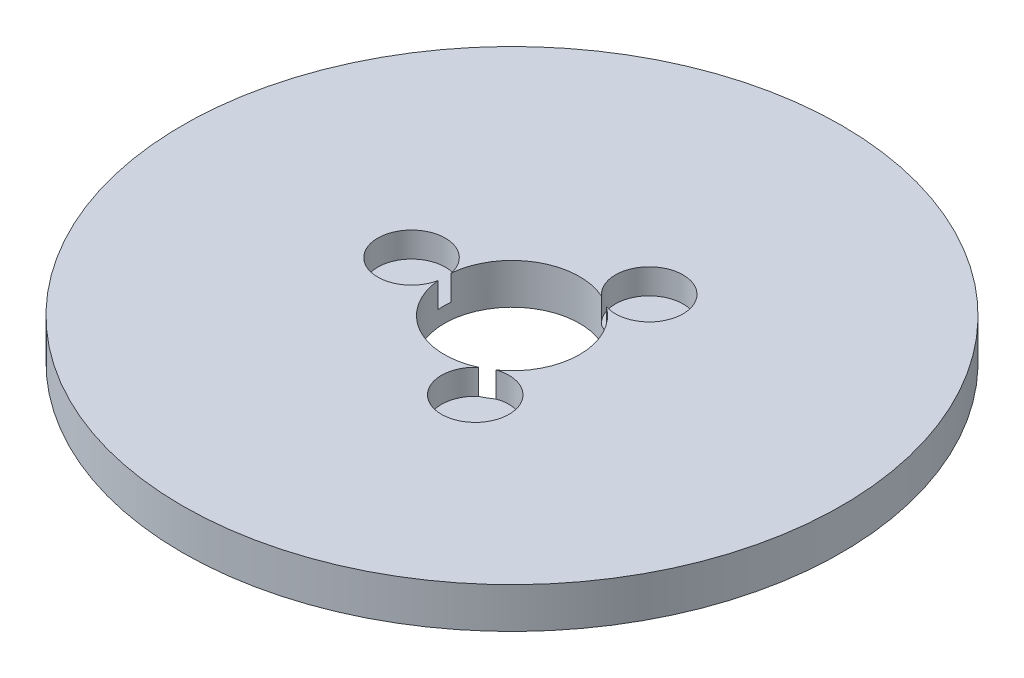
SolidWorks part; units mm, degrees
ref_plane "Front Plane" through (0, 0, 0) normal (0, 0, 1) x (1, 0, 0)
ref_plane "Top Plane" through (0, 0, 0) normal (0, 1, 0) x (1, 0, 0)
ref_plane "Right Plane" through (0, 0, 0) normal (1, 0, 0) x (0, 0, -1)
sketch "Sketch1" plane through (0, 0, 0) normal (0, 1, 0) x (1, 0, 0)
  circle A0 centre (0, 0) radius 97.5
  dimension "FLANGE_OD" = 195
extrude "Boss-Extrude1" add sketch "Sketch1" along normal blind 12
sketch "Sketch2" plane through (0, 0, 0) normal (0, 1, 0) x (1, 0, 0)
  circle A0 centre (0, 0) radius 20
  dimension "BORE_D" = 40
extrude "Cut-Extrude1" cut sketch "Sketch2" along normal through all
sketch "Sketch3" plane through (0, 12, 0) normal (0, 1, 0) x (1, 0, 0)
  circle A0 centre (0, 0) radius 29.7228 construction
  circle A1 centre (-29.7228, 0) radius 10
  dimension "BOLT_D" = 20
  dimension "BOLT_PCD" = 59.4457
extrude "Cut-Extrude2" cut sketch "Sketch3" against normal blind 7.448
pattern_circular "CirPattern1" count 3 over 360 about axis through (0, 0, 0) along (0, 1, 0) of "Cut-Extrude2"
